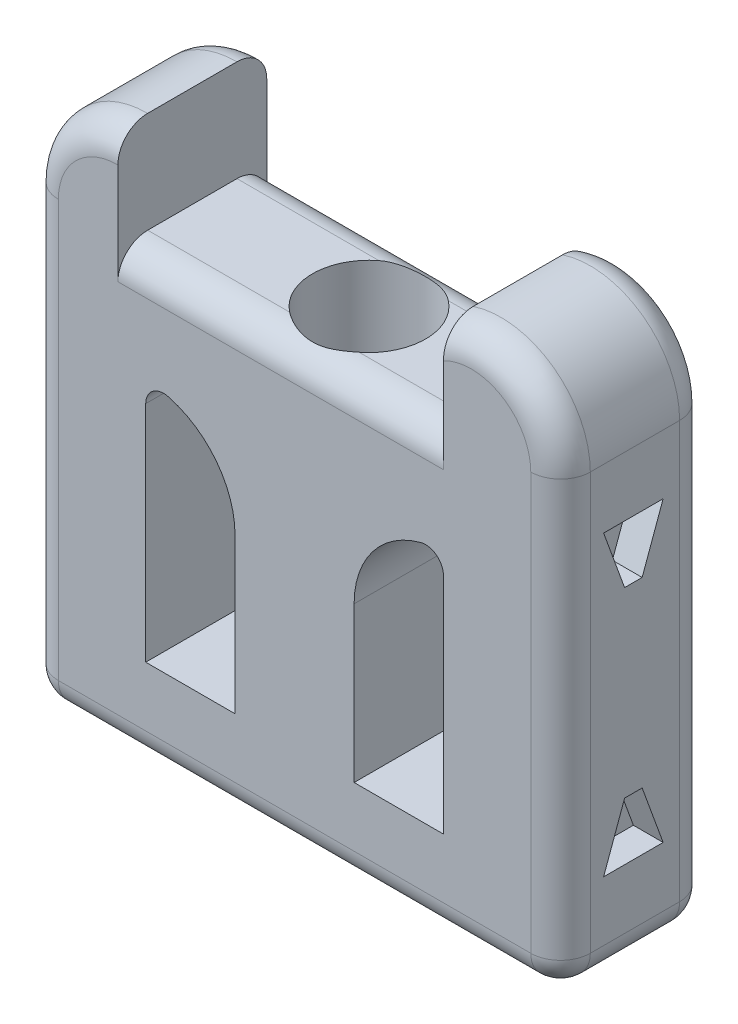
SolidWorks part; units mm, degrees
ref_plane "Front Plane" through (0, 0, 0) normal (0, 0, 1) x (1, 0, 0)
ref_plane "Top Plane" through (0, 0, 0) normal (0, 1, 0) x (1, 0, 0)
ref_plane "Right Plane" through (0, 0, 0) normal (1, 0, 0) x (0, 0, -1)
sketch "Sketch1" plane through (0, 0, 0) normal (0, 0, 1) x (1, 0, 0)
  line L1 (83.3423, -18.0015) -> (83.3423, -93)
  line L2 (83.3423, -93) -> (-6, -93)
  line L3 (-6, -93) -> (-6, -18.0015)
  line L4 (9, -3.0015) -> (9, -20)
  line L5 (9, -20) -> (63.6712, -20)
  line L6 (63.6712, -20) -> (63.6712, -3.7473)
  line L9 (63.6712, -40.3908) -> (63.6712, -78)
  line L10 (63.6712, -78) -> (48.6712, -78)
  line L11 (48.6712, -78) -> (48.6712, -52.01)
  line L12 (59.8453, -37.5061) -> (59.906, -37.4901)
  line L13 (38.6712, -93) -> (38.6712, -79.4088) construction
  line L14 (28.6712, -78) -> (28.6712, -52.01)
  line L15 (13.6712, -78) -> (28.6712, -78)
  line L16 (13.6712, -40.3908) -> (13.6712, -78)
  line L17 (17.4971, -37.5061) -> (17.4364, -37.4901)
  arc A0 (63.6712, -3.7473) -> (83.3423, -18.0015) centre (68.3423, -18.0015) cw
  arc A1 (9, -3.0015) -> (-6, -18.0015) centre (9, -18.0015) ccw
  arc A3 (48.6712, -52.01) -> (59.8453, -37.5061) centre (63.6712, -52.01) cw
  arc A4 (63.6712, -40.3908) -> (59.906, -37.4901) centre (60.6712, -40.3908) ccw
  arc A5 (28.6712, -52.01) -> (17.4971, -37.5061) centre (13.6712, -52.01) ccw
  arc A6 (13.6712, -40.3908) -> (17.4364, -37.4901) centre (16.6712, -40.3908) cw
  point P8 (84, -0.0023)
  point P11 (0, 0)
  dimension "D3" = 15
  dimension "D5" = 15
  dimension "D6" = 3
  dimension "D1" = 84
  dimension "D2" = 93
  dimension "D4" = 20
  dimension "D7" = 15
  dimension "D8" = 15
extrude "Boss-Extrude1" add sketch "Sketch1" along normal blind 25
sketch "Sketch2" plane through (0, -93, 0) normal (0, -1, 0) x (1, 0, 0)
  line L0 (83.3423, 25) -> (83.3423, 0) construction
  line L1 (-6, 25) -> (83.3423, 25) construction
  circle A0 centre (38.6712, 12.5) radius 9.5
  point P4 (83.3423, 12.5)
  point P7 (38.6712, 25)
  dimension "D1" = 19
extrude "Cut-Extrude1" cut sketch "Sketch2" against normal blind 89
fillet "Fillet1" radius 5 4 edges at (-6, -93, 12.5) (38.6712, -93, 25) (83.3423, -93, 12.5) (38.6712, -93, 0)
fillet "Fillet2" radius 5 12 edges at (81.8779, -91.5355, 1.4645) (77.1438, -5.8551, 0) (81.8779, -91.5355, 23.5355) (77.1438, -5.8551, 25) (-1.6066, -7.3949, 25) (-4.5355, -91.5355, 23.5355) (-1.6066, -7.3949, 0) (-4.5355, -91.5355, 1.4645) (83.3423, -53.0007, 0) (83.3423, -53.0007, 25) (-6, -53.0007, 25) (-6, -53.0007, 0)
fillet "Fillet3" radius 5 2 edges at (36.3356, -20, 0) (36.3356, -20, 25)
sketch "Sketch3" plane through (83.3423, 0, 0) normal (1, 0, 0) x (0, 0, -1)
  line L0 (-17.768, -28.0015) -> (-7.768, -28.0015)
  line L1 (-7.768, -28.0015) -> (-11.2942, -37.6896)
  line L2 (-11.2942, -37.6896) -> (-14.2418, -37.6896)
  line L3 (-14.2418, -37.6896) -> (-17.768, -28.0015)
  line L4 (-20, -18.0015) -> (-5, -18.0015) construction
  line L5 (-20, -53.0007) -> (-5, -53.0007) construction
  line L6 (-20, -18.0015) -> (-20, -88) construction
  line L7 (-5, -88) -> (-5, -18.0015) construction
  line L8 (-11.2942, -68.3119) -> (-14.2418, -68.3119)
  line L9 (-7.768, -78) -> (-11.2942, -68.3119)
  line L10 (-17.768, -78) -> (-7.768, -78)
  line L11 (-14.2418, -68.3119) -> (-17.768, -78)
  dimension "D1" = 10
  dimension "D2" = 70
  dimension "D3" = 70
  dimension "D4" = 10
extrude "Cut-Extrude2" cut sketch "Sketch3" against normal blind 5
ref_plane "Plane1" through (38.6712, 0, 0) normal (1, 0, 0) x (0, 0, -1)
mirror "Mirror1" about plane through (38.6712, 0, 0) normal (1, 0, 0) of "Cut-Extrude2"
